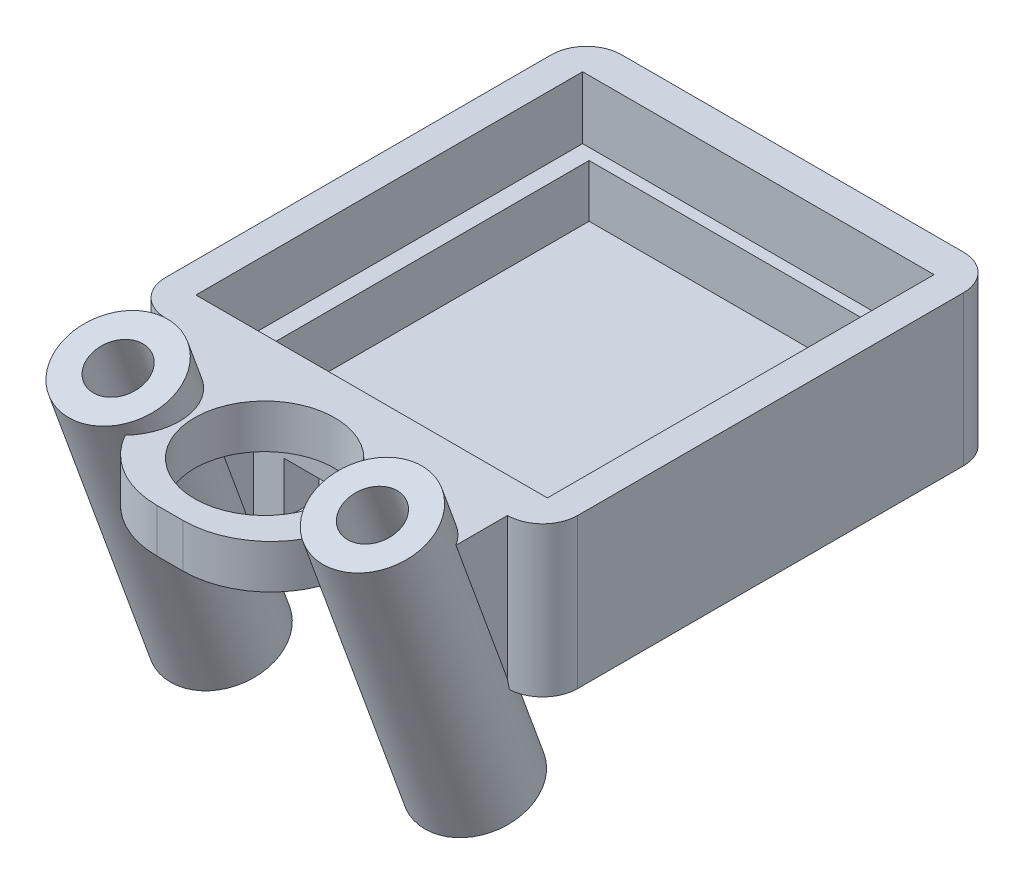
SolidWorks part; units mm, degrees
ref_plane "Front Plane" through (0, 0, 0) normal (0, 0, 1) x (1, 0, 0)
ref_plane "Top Plane" through (0, 0, 0) normal (0, 1, 0) x (1, 0, 0)
ref_plane "Right Plane" through (0, 0, 0) normal (1, 0, 0) x (0, 0, -1)
sketch "Sketch1" plane through (0, 0, 0) normal (0, 1, 0) x (1, 0, 0)
  line L1 (-11.75, -13) -> (11.75, -13)
  line L2 (-11.75, -13) -> (-11.75, 13)
  line L3 (-11.75, 13) -> (11.75, 13)
  line L4 (11.75, -13) -> (11.75, 13)
  line L5 (-11.75, -13) -> (11.75, 13) construction
  line L6 (-11.75, 13) -> (11.75, -13) construction
  line L7 (-9, 10.4) -> (9, 10.4)
  line L8 (-9, 10.4) -> (-9, -13)
  line L9 (-9, -13) -> (9, -13)
  line L10 (9, 10.4) -> (9, -13)
  point P0 (0, 0)
  dimension "D1" = 23.5
  dimension "D2" = 26
  dimension "D3" = 18
  dimension "D4" = 23.4
  dimension "D5" = 2.6
  dimension "D6" = 2.75
extrude "Boss-Extrude1" add sketch "Sketch1" along normal blind 8.55 contours L7 L10 L1 L4 L3 L2 L8 region at (-11.3995, 0, 0)
extrude "Boss-Extrude2" add sketch "Sketch1<4>" along normal blind 2 contours L10 L7 L8 L1 region at (0, 0, 1.3)
sketch "Sketch1<4>" plane through (0, 0, 0) normal (0, 1, 0) x (1, 0, 0) same geometry as "Sketch1"
sketch "Sketch2" plane through (0, 8.55, 0) normal (0, 1, 0) x (1, 0, 0)
  line L0 (9, -13) -> (11.75, -13) construction
  line L2 (-10.02, 11.05) -> (10.02, 11.05)
  line L3 (-10.02, 11.05) -> (-10.02, -13)
  line L4 (-10.02, -13) -> (10.02, -13)
  line L5 (10.02, 11.05) -> (10.02, -13)
  line L6 (-9, 10.4) -> (-9, -13) construction
  line L7 (9, 10.4) -> (9, -13) construction
  line L8 (-9, 10.4) -> (9, 10.4) construction
  dimension "D1" = 1.02
  dimension "D2" = 1.02
  dimension "D3" = 0.65
extrude "Cut-Extrude1" cut sketch "Sketch2" against normal blind 3.55
sketch "Sketch3" plane through (0, 0, 13) normal (0, 0, 1) x (1, 0, 0)
  line L0 (-11.75, 0) -> (11.75, 0) construction
  line L1 (-11.75, 8.55) -> (-3, 8.55)
  line L2 (-11.75, 8.55) -> (-11.75, 0)
  line L3 (-11.75, 0) -> (-3, 0)
  line L4 (-3, 5) -> (-3, 2)
  line L5 (10.02, 8.55) -> (-10.02, 8.55) construction
  line L6 (3, 8.55) -> (11.75, 8.55)
  line L7 (3, 5) -> (3, 2)
  line L8 (3, 0) -> (11.75, 0)
  line L9 (11.75, 8.55) -> (11.75, 0)
  line L10 (10.02, 5) -> (-10.02, 5) construction
  line L11 (-3, 8.55) -> (3, 8.55)
  line L13 (-3, 5) -> (3, 5)
  line L15 (-9, 2) -> (9, 2) construction
  line L16 (-3, 2) -> (3, 2)
  line L18 (-3, 0) -> (3, 0)
  dimension "D1" = 6
  dimension "D2" = 8.75
extrude "Boss-Extrude4" add sketch "Sketch3" against normal blind 2
fillet "Fillet1" radius 2 4 edges at (11.75, 4.275, 13) (11.75, 4.275, -13) (-11.75, 4.275, -13) (-11.75, 4.275, 13)
sketch "Sketch5" plane through (11.75, 0, 0) normal (1, 0, 0) x (0, 0, -1)
  line L0 (-13, 0) -> (-16.1119, 8.55)
  line L1 (-13, 0) -> (-13, 8.55) construction
  line L2 (-13, 8.55) -> (-16.1119, 8.55)
  line L3 (-13, 8.55) -> (-13, 0)
  dimension "D1" = 20
extrude "Boss-Extrude5" add sketch "Sketch5" against normal blind 23.5
sketch "Sketch6" plane through (0, 8.55, 0) normal (0, 1, 0) x (1, 0, 0)
  line L0 (-11.75, -16.1119) -> (11.75, -16.1119) construction
  line L1 (-11.75, -13) -> (-9.75, -13)
  line L2 (-11.75, -13) -> (-11.75, -16.1119)
  line L3 (-11.75, -16.1119) -> (-9.75, -16.1119)
  line L4 (-9.75, -13) -> (-9.75, -16.1119)
  line L6 (11.75, -13) -> (9.75, -13)
  line L7 (11.75, -13) -> (11.75, -16.1119)
  line L8 (11.75, -16.1119) -> (9.75, -16.1119)
  line L9 (9.75, -13) -> (9.75, -16.1119)
  line L10 (-4.75, -13) -> (4.75, -13)
  line L11 (-4.75, -13) -> (-4.75, -16.1119)
  line L12 (-4.75, -16.1119) -> (4.75, -16.1119)
  line L13 (4.75, -13) -> (4.75, -16.1119)
  dimension "D1" = 2
  dimension "D2" = 2
  dimension "D3" = 5
  dimension "D4" = 5
extrude "Cut-Extrude2" cut sketch "Sketch6" against normal blind 23
sketch "Sketch7" plane through (0, -4.1781, 11.4793) normal (0, -0.342, 0.9397) x (1, 0, 0)
  line L0 (4.75, 4.4463) -> (4.75, 13.545) construction
  line L1 (4.75, 13.545) -> (9.75, 13.545)
  line L2 (4.75, 13.545) -> (4.75, 12.254)
  line L3 (4.75, 12.254) -> (9.75, 12.254)
  line L4 (9.75, 13.545) -> (9.75, 12.254)
  line L5 (4.75, 13.545) -> (9.75, 13.545) construction
  line L6 (9.75, 13.545) -> (9.75, 4.4463) construction
extrude "Boss-Extrude6" add sketch "Sketch7" along normal blind 1
sketch "Sketch8" plane through (0, 12.7281, 4.6327) normal (0, 0.9397, 0.342) x (1, 0, 0)
  line L1 (4.75, -12.216) -> (9.75, -12.216) construction
  line L2 (-9.75, -12.216) -> (-4.75, -12.216) construction
  circle A1 centre (7.25, -13.716) radius 3
  circle A2 centre (-7.25, -13.716) radius 3
  circle A3 centre (-7.25, -13.716) radius 1.5
  circle A4 centre (7.25, -13.716) radius 1.5
  point P9 (-7.25, -12.216)
  line M6 (4.75, -13.216) -> (9.75, -13.216)
  dimension "D1" = 1.5
  dimension "D3" = 0
  dimension "D2" = 1.5
  dimension "D4" = 14.5
extrude "Boss-Extrude11" add sketch "Sketch8" against normal blind 15 and the other way blind 2 contours A1 | A2
extrude "Cut-Extrude3" cut sketch "Sketch8<5>" against normal blind 15 and the other way blind 2 contours A3 | A4 M6 | A4 M6 region at (-7.25, 8.037, 17.5215) region at (7.25, 7.9081, 17.8754) region at (7.25, 8.3497, 16.6624)
sketch "Sketch8<5>" plane through (0, 12.7281, 4.6327) normal (0, 0.9397, 0.342) x (1, 0, 0) same geometry as "Sketch8"
sketch "Sketch9" plane through (0, 8.55, 0) normal (0, 1, 0) x (1, 0, 0)
sketch "Sketch10" plane through (0, 8.55, 0) normal (0, 1, 0) x (1, 0, 0)
  line L0 (10.02, -11) -> (-10.02, -11) construction
  line L1 (-5.75, -11) -> (5.75, -11)
  line L2 (-5.75, -11) -> (-5.75, -17.5)
  line L3 (-0.75, -22.5) -> (0.75, -22.5)
  line L4 (5.75, -11) -> (5.75, -17.5)
  line L5 (4.75, -13) -> (-4.75, -13) construction
  line L6 (-11.75, -11) -> (-11.75, 11) construction
  circle A0 centre (0, -17.1) radius 4
  arc A1 (0.75, -22.5) -> (5.75, -17.5) centre (0.75, -17.5) ccw
  arc A2 (-5.75, -17.5) -> (-0.75, -22.5) centre (-0.75, -17.5) ccw
  point P14 (5.75, -22.5)
  point P17 (-5.75, -22.5)
  dimension "D2" = 4.1
  dimension "D5" = 5
  dimension "D1" = 11.5
  dimension "D3" = 11.5
  dimension "D4" = 6
extrude "Boss-Extrude13" add sketch "Sketch10" against normal blind 2.5
